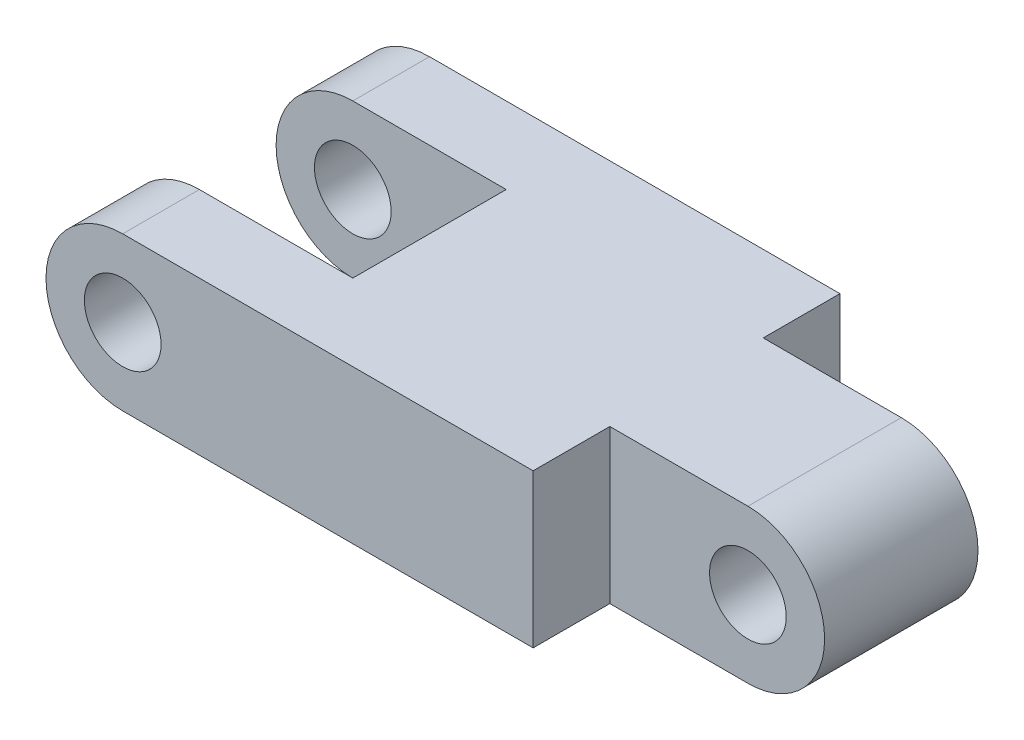
SolidWorks part; units mm, degrees
ref_plane "Front Plane" through (0, 0, 0) normal (0, 0, 1) x (1, 0, 0)
ref_plane "Top Plane" through (0, 0, 0) normal (0, 1, 0) x (1, 0, 0)
ref_plane "Right Plane" through (0, 0, 0) normal (1, 0, 0) x (0, 0, -1)
sketch "Sketch1" plane through (0, 0, 0) normal (0, 0, 1) x (1, 0, 0)
  line L0 (0, 10) -> (53.5123, 10)
  line L1 (53.5123, 10) -> (53.5123, -10)
  line L2 (53.5123, -10) -> (0, -10)
  circle A0 centre (0, 0) radius 10
  dimension "D1" = 20
extrude "Boss-Extrude1" add sketch "Sketch1" along normal blind 40 contours A0 | A0 L2 L1 L0 region at (30.6286, 0, 0) region at (0, 0, 0)
ref_plane "Plane1" through (0, 0, 0) normal (1, 0, 0) x (0, 0, -1)
sketch "Sketch2" plane through (0, 0, 0) normal (1, 0, 0) x (0, 0, -1)
  line L0 (0, 0) -> (-40, 0) construction
  line L1 (-40, 10) -> (-40, -10) construction
  line L3 (-10, 14.4724) -> (-30, 14.4724)
  line L4 (-10, 14.4724) -> (-10, -14.4724)
  line L5 (-10, -14.4724) -> (-30, -14.4724)
  line L6 (-30, 14.4724) -> (-30, -14.4724)
  line L7 (-10, 14.4724) -> (-30, -14.4724) construction
  line L8 (-10, -14.4724) -> (-30, 14.4724) construction
  point P5 (-20, 0)
  dimension "D1" = 20
extrude "Cut-Extrude1" cut sketch "Sketch2" against normal blind 40 and the other way blind 20
sketch "Sketch3" plane through (0, 0, 40) normal (0, 0, 1) x (1, 0, 0)
  circle A0 centre (0, 0) radius 5
  dimension "D1" = 10
extrude "Cut-Extrude3" cut sketch "Sketch3" against normal blind 40
ref_plane "Plane2" through (0, 0, 30) normal (0, 0, 1) x (1, 0, 0)
sketch "Sketch5" plane through (0, 0, 30) normal (0, 0, 1) x (1, 0, 0)
  line L0 (53.5123, -10) -> (0, -10) construction
  line L1 (53.5123, 10) -> (71.5123, 10)
  line L2 (53.5123, 10) -> (53.5123, -10)
  line L3 (53.5123, -10) -> (71.5123, -10)
  line L4 (71.5123, 10) -> (71.5123, -10)
  circle A0 centre (71.5123, 0) radius 10
  circle A1 centre (71.5123, 0) radius 5
  dimension "D1" = 10
  dimension "D2" = 18
extrude "Boss-Extrude2" add sketch "Sketch5" against normal blind 20 contours A0 L1 L2 L3 | A1 L4 A0 | A1 L4 A0 region at (58.8308, 0, 30) region at (78.4252, 6.913, 30) region at (71.2887, 7.5, 30)
